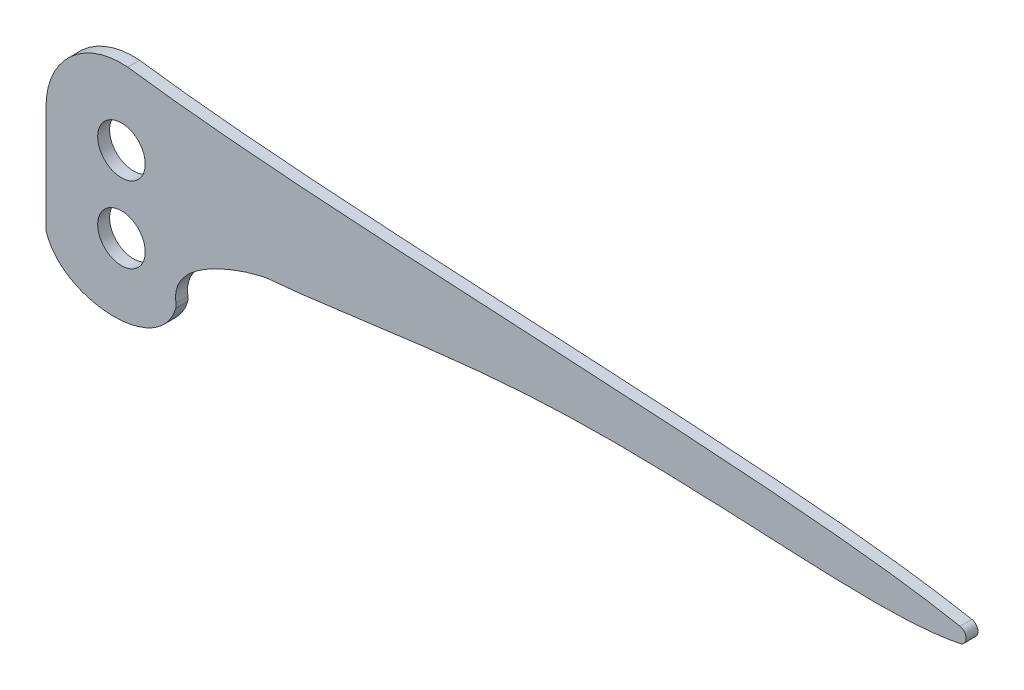
SolidWorks part; units mm, degrees
ref_plane "Front Plane" through (0, 0, 0) normal (0, 0, 1) x (1, 0, 0)
ref_plane "Top Plane" through (0, 0, 0) normal (0, 1, 0) x (1, 0, 0)
ref_plane "Right Plane" through (0, 0, 0) normal (1, 0, 0) x (0, 0, -1)
sketch "Sketch1" plane through (0, 0, 0) normal (0, 0, 1) x (1, 0, 0)
  line L0 (0, 0) -> (0, -25.4) construction
  line L1 (-25.1919, 0) -> (-25.1919, -35.2154)
  arc A1 (279.8894, 2.3729) -> (279.9348, -2.6026) centre (279.4, -0.1195) cw
  arc A2 (2.0902, 25.105) -> (-25.1919, 0) centre (0, 0) ccw
  circle A5 centre (0, -25.4) radius 7.9375
  circle A6 centre (0, 0) radius 7.9375
  arc A8 (18.2122, -35.0564) -> (18.1176, -36.6407) centre (14.8556, -35.6511) cw
  arc A9 (-25.1919, -35.2154) -> (-25.0041, -36.3312) centre (-21.783, -35.2154) ccw
  spline S0 degree 3 poles (2.0902, 25.105) (29.3726, 21.3189) (128.0417, 14.5406) (239.5484, 10.2935) (279.8894, 2.3729) knots 0.008543 0.008543 0.008543 0.008543 0.340595 0.941395 0.941395 0.941395 0.941395
  spline S1 degree 3 poles (50.3146, -12.4878) (67.829, -11.2174) (162.8512, 6.0974) (250.0383, -9.0418) (279.9348, -2.6026) knots 0.235846 0.235846 0.235846 0.235846 0.495201 0.941477 0.941477 0.941477 0.941477
  spline S2 degree 3 poles (18.2122, -35.0564) (15.7223, -21.0033) (45.0837, -12.5774) (50.3146, -12.4878) knots 0.243689 0.243689 0.243689 0.243689 1 1 1 1
  spline S3 degree 3 poles (-25.0041, -36.3312) (-24.3022, -38.3573) (-17.5003, -49.4729) (6.4866, -52.353) (16.8283, -40.8908) (18.1176, -36.6407) knots 0.011286 0.011286 0.011286 0.011286 0.130988 0.750185 0.983992 0.983992 0.983992 0.983992
  point P3 (76.2, 0)
  dimension "D1" = 3.4089
  dimension "D2" = 2.54
  dimension "D3" = 15.875
  dimension "D6" = 279.4
extrude "Boss-Extrude1" add sketch "Sketch1" along normal blind 3.9688 contours S1 A1 S0 region at (77.4581, -1.4365, 0)
scale "Scale1" scale about centroid uniform scaling yes scale factor 0.75
